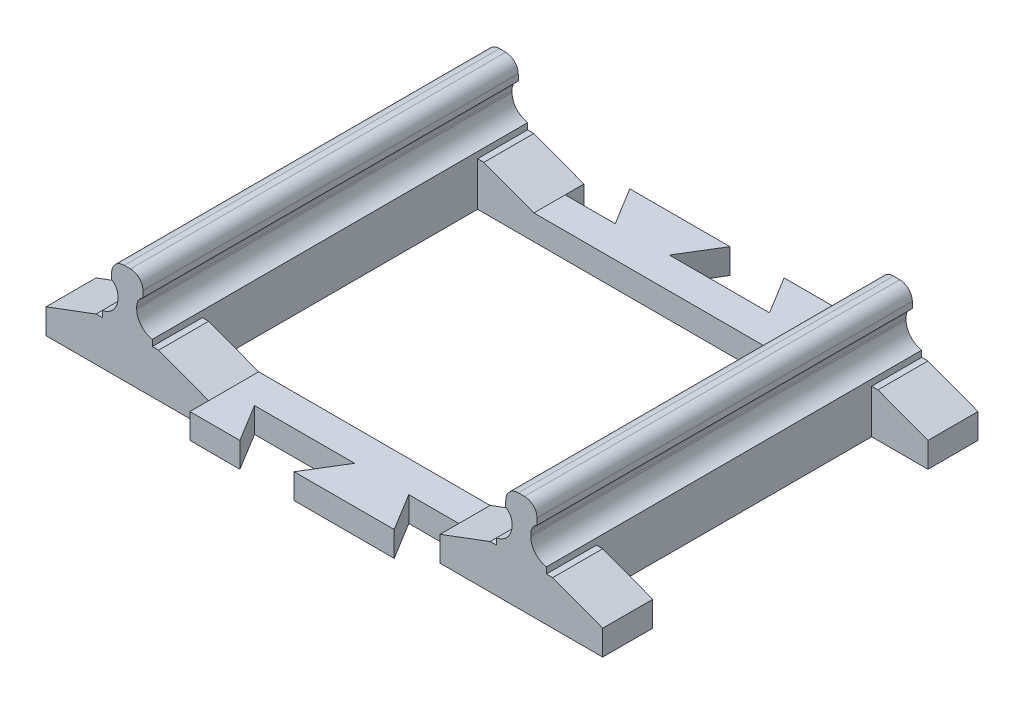
SolidWorks part; units mm, degrees
other "标注1"
sketch "草图3" plane through (-22.25, 4, -10) normal (-0.231, 0.6469, -0.7268) x (-0.9696, -0.2151, 0.1167)
other "标注2"
sketch "草图4" plane through (22.25, 8, -30) normal (0.0083, 0.0567, -0.9984) x (-0.9991, 0.0415, -0.0059)
ref_plane "前视基准面" through (0, 0, 0) normal (0, 0, 1) x (1, 0, 0)
ref_plane "上视基准面" through (0, 0, 0) normal (0, 1, 0) x (1, 0, 0)
ref_plane "右视基准面" through (0, 0, 0) normal (1, 0, 0) x (0, 0, -1)
other "Configuration Table"
sketch "草图1" plane through (0, 0, 0) normal (0, 1, 0) x (1, 0, 0)
  line L0 (-13.75, 9.5) -> (-13.75, -9.5)
  line L13 (-17.75, -9.5) -> (17.75, -9.5)
  line L21 (-17.75, -9.5) -> (-17.75, 9.5)
  line L22 (-17.75, 9.5) -> (17.75, 9.5)
  line L23 (17.75, -9.5) -> (17.75, 9.5)
  line L24 (-17.75, -9.5) -> (17.75, 9.5) construction
  line L25 (-17.75, 9.5) -> (17.75, -9.5) construction
  line L27 (13.75, 9.5) -> (13.75, -9.5)
  line L29 (-13.75, 0) -> (13.75, 0) construction
  line L32 (-22.25, 9.5) -> (22.25, 9.5)
  line L33 (-22.25, 9.5) -> (-22.25, 1.5)
  line L34 (-22.25, 1.5) -> (22.25, 1.5)
  line L35 (22.25, 9.5) -> (22.25, 1.5)
  point P0 (0, 0)
  point P15 (0, 1.5)
  dimension "D3" = 27.5
  dimension "D4" = 8
  dimension "D1" = 35.5
  dimension "D2" = 19
  dimension "D5" = 44.5
extrude "凸台-拉伸1" add sketch "草图1" along normal blind 4 contours L34 L21 L13 L0 | L34 L27 L13 L23 | L27 L34 L23 L22 | L21 L34 L0 L22 region at (-15.75, 0, -5.5) region at (-15.75, 0, 4) region at (15.75, 0, -5.5) region at (15.75, 0, 4)
extrude "凸台-拉伸2" add sketch "草图1<7>" along normal blind 3.5 contours L34 L35 L32 L33
sketch "草图1<7>" plane through (0, 0, 0) normal (0, 1, 0) x (1, 0, 0) same geometry as "草图1"
sketch "草图2" plane through (0, 0, -9.5) normal (0, 0, -1) x (-1, 0, 0)
  line L0 (18.25, 3.5) -> (22.25, 2)
  line L1 (22.25, 3.5) -> (18.25, 3.5)
  line L2 (22.25, 3.5) -> (22.25, 2)
  line L3 (22.25, 2) -> (18.25, 2) construction
  line L4 (18.25, 3.5) -> (18.25, 2) construction
  line L5 (-22.25, 2) -> (-18.25, 3.5)
  line L6 (-22.25, 3.5) -> (-18.25, 3.5)
  line L7 (-22.25, 3.5) -> (-22.25, 2)
  line L8 (-22.25, 2) -> (-18.25, 2) construction
  line L9 (-18.25, 3.5) -> (-18.25, 2) construction
  line L10 (13.75, 3.5) -> (-13.75, 3.5) construction
  line L11 (-13.25, 3.5) -> (-9.25, 3.5)
  line L12 (-13.25, 3.5) -> (-13.25, 2) construction
  line L13 (-13.25, 2) -> (-9.25, 2) construction
  line L14 (-9.25, 3.5) -> (-9.25, 2)
  line L15 (-13.75, 3.5) -> (-13.25, 3.5) construction
  line L16 (13.25, 3.5) -> (9.25, 3.5)
  line L17 (13.25, 3.5) -> (13.25, 2) construction
  line L18 (13.25, 2) -> (9.25, 2) construction
  line L19 (9.25, 3.5) -> (9.25, 2)
  line L20 (13.25, 3.5) -> (13.75, 3.5) construction
  line L21 (17.75, 3.5) -> (18.25, 3.5) construction
  line L22 (-13.25, 3.5) -> (-9.25, 2)
  line L23 (9.25, 2) -> (13.25, 3.5)
  line L24 (-9.25, 2) -> (9.25, 2)
  line L25 (-9.25, 3.5) -> (9.25, 3.5)
  line L26 (-15.75, 4) -> (-15.75, 6.5) construction
  line L27 (14.5, 8) -> (17, 8)
  line L28 (14.5, 8) -> (14.5, 6.5)
  line L29 (14.5, 6.5) -> (17, 6.5)
  line L30 (17, 8) -> (17, 6.5)
  line L31 (-17, 8) -> (-14.5, 8)
  line L32 (-17, 8) -> (-17, 6.5)
  line L33 (-17, 6.5) -> (-14.5, 6.5)
  line L34 (-14.5, 8) -> (-14.5, 6.5)
  line L35 (-13.75, 4) -> (-17.75, 4) construction
  line L36 (15.75, 6.5) -> (15.75, 4) construction
  line L37 (17.75, 4) -> (13.75, 4) construction
  line L38 (15, 6.5) -> (15, 4)
  line L39 (16.5, 6.5) -> (16.5, 4)
  line L40 (16.5, 4) -> (15.75, 4)
  line L41 (15.75, 4) -> (15, 4)
  line L42 (-16.5, 6.5) -> (-16.5, 4)
  line L43 (-16.5, 4) -> (-15.75, 4)
  line L44 (-15.75, 4) -> (-15, 4)
  line L45 (-15, 4) -> (-15, 6.5)
  line M9 (22.25, 3.5) -> (17.75, 3.5)
  line M11 (17.75, 4) -> (13.75, 4)
  line M13 (13.75, 3.5) -> (-13.75, 3.5)
  line M15 (-13.75, 4) -> (-17.75, 4)
  line M17 (-17.75, 3.5) -> (-22.25, 3.5)
  line M18 (-22.25, 3.5) -> (-22.25, 0)
  line M20 (22.25, 0) -> (22.25, 3.5)
  dimension "D1" = 4
  dimension "D2" = 1.5
  dimension "D3" = 2.5
  dimension "D4" = 1.5
  dimension "D5" = 2.5
  dimension "D6" = 1.5
extrude "切除-拉伸1" cut sketch "草图2" against normal through all contours L14 L24 L19 M13 | L19 L23 M13 | L22 L14 M13 | L5 M18 M17 | L0 M9 M20 region at (-20.9167, 3, -9.5) region at (20.9167, 3, -9.5) region at (10.5833, 3, -9.5) region at (0, 2.75, -9.5) region at (-10.5833, 3, -9.5)
extrude "凸台-拉伸4" add sketch "草图2<3>" against normal through all contours L34 L31 L32 L33 | L45 L33 L42 M15 | L30 L27 L28 L29 | L39 L29 L38 M11 region at (-15.75, 7.25, -9.5) region at (-15.75, 5.25, -9.5) region at (15.75, 7.25, -9.5) region at (15.75, 5.25, -9.5)
sketch "草图2<3>" plane through (0, 0, -9.5) normal (0, 0, -1) x (-1, 0, 0) same geometry as "草图2"
fillet "圆角1" radius 1 4 edges at (-16.5, 6.5, 0) (-15, 6.5, 0) (15, 6.5, 0) (16.5, 6.5, 0)
fillet "圆角2" radius 1.5 4 edges at (16.5, 4, 0) (15, 4, 0) (-15, 4, 0) (-16.5, 4, 0)
fillet "圆角3" radius 1 4 edges at (-17, 8, 0) (14.5, 8, 0) (17, 8, 0) (-14.5, 8, 0)
sketch "草图8" plane through (22.25, 0, 0) normal (1, 0, 0) x (0, 0, -1)
  line L0 (5.5, 0) -> (5.5, 18.5305)
  line L1 (9.5, 0) -> (1.5, 0) construction
mirror "镜向2" about plane through (0, 4, 9.5) normal (0, 0, -1) of bodies 192
sketch "草图9" plane through (0, 2, 0) normal (0, 1, 0) x (1, 0, 0)
  line L0 (-22.25, 5.5) -> (-9.25, 5.5)
  line L1 (-22.25, 1.5) -> (-22.25, 9.5) construction
  line L2 (-9.25, 1.5) -> (-9.25, 9.5) construction
  line L3 (-9.25, 5.5) -> (-9.25, 4)
  line L4 (-9.25, 4) -> (-5.25, 4)
  line L5 (-5.25, 4) -> (-7.0833, 7)
  line L6 (-7.0833, 7) -> (0.9167, 7)
  line L7 (0.9167, 7) -> (-0.9167, 4)
  line L8 (-0.9167, 4) -> (7.0833, 4)
  line L9 (7.0833, 4) -> (5.25, 7)
  line L10 (9.25, 1.5) -> (9.25, 9.5) construction
  line L11 (9.25, 5.5) -> (22.25, 5.5)
  line L12 (5.25, 7) -> (9.25, 7)
  line L13 (-22.25, 5.5) -> (-22.25, 9.5)
  line L14 (9.25, 7) -> (9.25, 5.5)
  line L15 (-22.25, 9.5) -> (22.25, 9.5)
  line L16 (22.25, 9.5) -> (22.25, 5.5)
  line L17 (22.25, 1.5) -> (22.25, 9.5) construction
  line L18 (-22.25, -24.5) -> (-9.25, -24.5)
  line L19 (-22.25, -20.5) -> (-22.25, -28.5) construction
  line L20 (-9.25, -20.5) -> (-9.25, -28.5) construction
  line L21 (-9.25, -24.5) -> (-9.25, -26)
  line L22 (-9.25, -26) -> (-5.25, -26)
  line L23 (-5.25, -26) -> (-7.0833, -23)
  line L24 (-7.0833, -23) -> (0.9167, -23)
  line L25 (0.9167, -23) -> (-0.9167, -26)
  line L26 (-0.9167, -26) -> (7.0833, -26)
  line L27 (7.0833, -26) -> (5.25, -23)
  line L28 (5.25, -23) -> (9.25, -23)
  line L29 (9.25, -20.5) -> (9.25, -28.5) construction
  line L30 (9.25, -23) -> (9.25, -24.5)
  line L31 (9.25, -24.5) -> (22.25, -24.5)
  line L32 (22.25, -20.5) -> (22.25, -28.5) construction
  line L33 (22.25, -24.5) -> (22.25, -28.5)
  line L34 (22.25, -28.5) -> (-22.25, -28.5)
  line L35 (-22.25, -28.5) -> (-22.25, -24.5)
  dimension "D1" = 3
  dimension "D2" = 8
  dimension "D3" = 4
extrude "切除-拉伸2" cut sketch "草图9" against normal through all both and the other way through all
